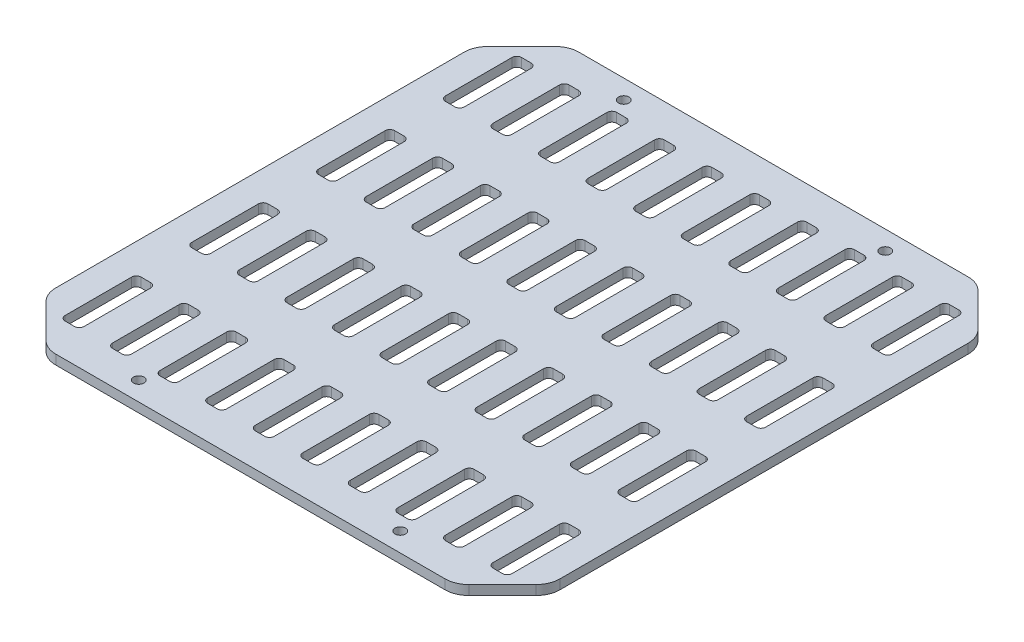
SolidWorks part; units mm, degrees
material "椴木"
ref_plane "前视基准面" through (0, 0, 0) normal (0, 0, 1) x (1, 0, 0)
ref_plane "上视基准面" through (0, 0, 0) normal (0, 1, 0) x (1, 0, 0)
ref_plane "右视基准面" through (0, 0, 0) normal (1, 0, 0) x (0, 0, -1)
sketch "草图1" plane through (0, 0, 0) normal (0, 1, 0) x (1, 0, 0)
  line L0 (-99.3153, 0) -> (94.5405, 0) construction
  line L1 (-53, 55) -> (53, 55)
  line L2 (-53, 55) -> (-53, -55)
  line L3 (-53, -55) -> (53, -55)
  line L4 (53, 55) -> (53, -55)
  line L5 (-53, 55) -> (53, -55) construction
  line L6 (-53, -55) -> (53, 55) construction
  line L7 (0, 84.1554) -> (0, -93.2275) construction
  line L8 (-61.5369, 40) -> (67.7359, 40) construction
  line L9 (-37, 48) -> (-37, 32)
  line L10 (-47, 48) -> (-43, 48)
  line L11 (-47, 48) -> (-47, 32)
  line L12 (-47, 32) -> (-43, 32)
  line L13 (-43, 48) -> (-43, 32)
  line L14 (-47, 48) -> (-43, 32) construction
  line L15 (-47, 32) -> (-43, 48) construction
  line L16 (-37, 48) -> (-33, 48)
  line L17 (-33, 48) -> (-33, 32)
  line L18 (-37, 32) -> (-33, 32)
  line L19 (-27, 48) -> (-27, 32)
  line L20 (-27, 48) -> (-23, 48)
  line L21 (-23, 48) -> (-23, 32)
  line L22 (-27, 32) -> (-23, 32)
  line L23 (-17, 48) -> (-17, 32)
  line L24 (-17, 48) -> (-13, 48)
  line L25 (-13, 48) -> (-13, 32)
  line L26 (-17, 32) -> (-13, 32)
  line L27 (-7, 48) -> (-7, 32)
  line L28 (-7, 48) -> (-3, 48)
  line L29 (-3, 48) -> (-3, 32)
  line L30 (-7, 32) -> (-3, 32)
  line L31 (3, 48) -> (3, 32)
  line L32 (3, 48) -> (7, 48)
  line L33 (7, 48) -> (7, 32)
  line L34 (3, 32) -> (7, 32)
  line L35 (13, 48) -> (13, 32)
  line L36 (13, 48) -> (17, 48)
  line L37 (17, 48) -> (17, 32)
  line L38 (13, 32) -> (17, 32)
  line L39 (23, 48) -> (23, 32)
  line L40 (23, 48) -> (27, 48)
  line L41 (27, 48) -> (27, 32)
  line L42 (23, 32) -> (27, 32)
  line L43 (33, 48) -> (33, 32)
  line L44 (33, 48) -> (37, 48)
  line L45 (37, 48) -> (37, 32)
  line L46 (33, 32) -> (37, 32)
  line L47 (43, 48) -> (43, 32)
  line L48 (43, 48) -> (47, 48)
  line L49 (47, 48) -> (47, 32)
  line L50 (43, 32) -> (47, 32)
  line L51 (-37, 21.3333) -> (-37, 5.3333)
  line L52 (-37, 21.3333) -> (-33, 21.3333)
  line L53 (-33, 21.3333) -> (-33, 5.3333)
  line L54 (-37, 5.3333) -> (-33, 5.3333)
  line L55 (-27, 21.3333) -> (-27, 5.3333)
  line L56 (-27, 21.3333) -> (-23, 21.3333)
  line L57 (-23, 21.3333) -> (-23, 5.3333)
  line L58 (-27, 5.3333) -> (-23, 5.3333)
  line L59 (-17, 21.3333) -> (-17, 5.3333)
  line L60 (-17, 21.3333) -> (-13, 21.3333)
  line L61 (-13, 21.3333) -> (-13, 5.3333)
  line L62 (-17, 5.3333) -> (-13, 5.3333)
  line L63 (-7, 21.3333) -> (-7, 5.3333)
  line L64 (-7, 21.3333) -> (-3, 21.3333)
  line L65 (-3, 21.3333) -> (-3, 5.3333)
  line L66 (-7, 5.3333) -> (-3, 5.3333)
  line L67 (3, 21.3333) -> (3, 5.3333)
  line L68 (3, 21.3333) -> (7, 21.3333)
  line L69 (7, 21.3333) -> (7, 5.3333)
  line L70 (3, 5.3333) -> (7, 5.3333)
  line L71 (13, 21.3333) -> (13, 5.3333)
  line L72 (13, 21.3333) -> (17, 21.3333)
  line L73 (17, 21.3333) -> (17, 5.3333)
  line L74 (13, 5.3333) -> (17, 5.3333)
  line L75 (23, 21.3333) -> (23, 5.3333)
  line L76 (23, 21.3333) -> (27, 21.3333)
  line L77 (27, 21.3333) -> (27, 5.3333)
  line L78 (23, 5.3333) -> (27, 5.3333)
  line L79 (33, 21.3333) -> (33, 5.3333)
  line L80 (33, 21.3333) -> (37, 21.3333)
  line L81 (37, 21.3333) -> (37, 5.3333)
  line L82 (33, 5.3333) -> (37, 5.3333)
  line L83 (43, 21.3333) -> (43, 5.3333)
  line L84 (43, 21.3333) -> (47, 21.3333)
  line L85 (47, 21.3333) -> (47, 5.3333)
  line L86 (43, 5.3333) -> (47, 5.3333)
  line L87 (-37, -5.3333) -> (-37, -21.3333)
  line L88 (-37, -5.3333) -> (-33, -5.3333)
  line L89 (-33, -5.3333) -> (-33, -21.3333)
  line L90 (-37, -21.3333) -> (-33, -21.3333)
  line L91 (-27, -5.3333) -> (-27, -21.3333)
  line L92 (-27, -5.3333) -> (-23, -5.3333)
  line L93 (-23, -5.3333) -> (-23, -21.3333)
  line L94 (-27, -21.3333) -> (-23, -21.3333)
  line L95 (-17, -5.3333) -> (-17, -21.3333)
  line L96 (-17, -5.3333) -> (-13, -5.3333)
  line L97 (-13, -5.3333) -> (-13, -21.3333)
  line L98 (-17, -21.3333) -> (-13, -21.3333)
  line L99 (-7, -5.3333) -> (-7, -21.3333)
  line L100 (-7, -5.3333) -> (-3, -5.3333)
  line L101 (-3, -5.3333) -> (-3, -21.3333)
  line L102 (-7, -21.3333) -> (-3, -21.3333)
  line L103 (3, -5.3333) -> (3, -21.3333)
  line L104 (3, -5.3333) -> (7, -5.3333)
  line L105 (7, -5.3333) -> (7, -21.3333)
  line L106 (3, -21.3333) -> (7, -21.3333)
  line L107 (13, -5.3333) -> (13, -21.3333)
  line L108 (13, -5.3333) -> (17, -5.3333)
  line L109 (17, -5.3333) -> (17, -21.3333)
  line L110 (13, -21.3333) -> (17, -21.3333)
  line L111 (23, -5.3333) -> (23, -21.3333)
  line L112 (23, -5.3333) -> (27, -5.3333)
  line L113 (27, -5.3333) -> (27, -21.3333)
  line L114 (23, -21.3333) -> (27, -21.3333)
  line L115 (33, -5.3333) -> (33, -21.3333)
  line L116 (33, -5.3333) -> (37, -5.3333)
  line L117 (37, -5.3333) -> (37, -21.3333)
  line L118 (33, -21.3333) -> (37, -21.3333)
  line L119 (43, -5.3333) -> (43, -21.3333)
  line L120 (43, -5.3333) -> (47, -5.3333)
  line L121 (47, -5.3333) -> (47, -21.3333)
  line L122 (43, -21.3333) -> (47, -21.3333)
  line L123 (-37, -32) -> (-37, -48)
  line L124 (-37, -32) -> (-33, -32)
  line L125 (-33, -32) -> (-33, -48)
  line L126 (-37, -48) -> (-33, -48)
  line L127 (-27, -32) -> (-27, -48)
  line L128 (-27, -32) -> (-23, -32)
  line L129 (-23, -32) -> (-23, -48)
  line L130 (-27, -48) -> (-23, -48)
  line L131 (-17, -32) -> (-17, -48)
  line L132 (-17, -32) -> (-13, -32)
  line L133 (-13, -32) -> (-13, -48)
  line L134 (-17, -48) -> (-13, -48)
  line L135 (-7, -32) -> (-7, -48)
  line L136 (-7, -32) -> (-3, -32)
  line L137 (-3, -32) -> (-3, -48)
  line L138 (-7, -48) -> (-3, -48)
  line L139 (3, -32) -> (3, -48)
  line L140 (3, -32) -> (7, -32)
  line L141 (7, -32) -> (7, -48)
  line L142 (3, -48) -> (7, -48)
  line L143 (13, -32) -> (13, -48)
  line L144 (13, -32) -> (17, -32)
  line L145 (17, -32) -> (17, -48)
  line L146 (13, -48) -> (17, -48)
  line L147 (23, -32) -> (23, -48)
  line L148 (23, -32) -> (27, -32)
  line L149 (27, -32) -> (27, -48)
  line L150 (23, -48) -> (27, -48)
  line L151 (33, -32) -> (33, -48)
  line L152 (33, -32) -> (37, -32)
  line L153 (37, -32) -> (37, -48)
  line L154 (33, -48) -> (37, -48)
  line L155 (43, -32) -> (43, -48)
  line L156 (43, -32) -> (47, -32)
  line L157 (47, -32) -> (47, -48)
  line L158 (43, -48) -> (47, -48)
  line L159 (-47, 21.3333) -> (-47, 5.3333)
  line L160 (-47, 21.3333) -> (-43, 21.3333)
  line L161 (-43, 21.3333) -> (-43, 5.3333)
  line L162 (-47, 5.3333) -> (-43, 5.3333)
  line L163 (-47, -5.3333) -> (-47, -21.3333)
  line L164 (-47, -5.3333) -> (-43, -5.3333)
  line L165 (-43, -5.3333) -> (-43, -21.3333)
  line L166 (-47, -21.3333) -> (-43, -21.3333)
  line L167 (-47, -32) -> (-47, -48)
  line L168 (-47, -32) -> (-43, -32)
  line L169 (-43, -32) -> (-43, -48)
  line L170 (-47, -48) -> (-43, -48)
  circle A0 centre (-27.5, 51) radius 1.1
  circle A1 centre (-27.5, 29) radius 1.1 construction
  circle A2 centre (27.5, 29) radius 1.1 construction
  circle A3 centre (27.5, 51) radius 1.1
  circle A4 centre (27.5, -29) radius 1.1 construction
  circle A5 centre (27.5, -51) radius 1.1
  circle A6 centre (-27.5, -29) radius 1.1 construction
  circle A7 centre (-27.5, -51) radius 1.1
  point P0 (0, 0)
  point P28 (-50.0057, 20.3333)
  point P29 (-45, 40)
  dimension "D3" = 2.2
  dimension "D1" = 106
  dimension "D2" = 110
  dimension "D4" = 22
  dimension "D5" = 55
  dimension "D6" = 102
  dimension "D7" = 4
  dimension "D8" = 16
  dimension "D9" = 6
  dimension "D10" = 10
  dimension "D11" = 4
extrude "凸台-拉伸1" add sketch "草图1" along normal blind 2
chamfer "倒角1" distance 10 angle 45 4 edges at (53, 1, -55) (53, 1, 55) (-53, 1, 55) (-53, 1, -55)
fillet "圆角1" radius 5 8 edges at (-53, 1, 45) (-43, 1, 55) (43, 1, 55) (53, 1, 45) (53, 1, -45) (43, 1, -55) (-43, 1, -55) (-53, 1, -45)
fillet "圆角2" radius 1 160 edges at (-43, 1, 32) (-47, 1, 32) (-47, 1, 48) (-43, 1, 48) (-43, 1, 5.3333) (-47, 1, 5.3333) (-47, 1, 21.3333) (-43, 1, 21.3333) (-43, 1, -21.3333) (-47, 1, -21.3333) (-47, 1, -5.3333) (-43, 1, -5.3333) (47, 1, 32) (43, 1, 32) (43, 1, 48) (47, 1, 48) (37, 1, 32) (33, 1, 32) (33, 1, 48) (37, 1, 48) (27, 1, 32) (23, 1, 32) (23, 1, 48) (27, 1, 48) (17, 1, 32) (13, 1, 32) (13, 1, 48) (17, 1, 48) (7, 1, 32) (3, 1, 32) (3, 1, 48) (7, 1, 48) (-3, 1, 32) (-7, 1, 32) (-7, 1, 48) (-3, 1, 48) (-13, 1, 32) (-17, 1, 32) (-17, 1, 48) (-13, 1, 48) (-23, 1, 32) (-27, 1, 32) (-27, 1, 48) (-23, 1, 48) (-33, 1, 32) (-37, 1, 32) (-37, 1, 48) (-33, 1, 48) (47, 1, 5.3333) (43, 1, 5.3333) (43, 1, 21.3333) (47, 1, 21.3333) (37, 1, 5.3333) (33, 1, 5.3333) (33, 1, 21.3333) (37, 1, 21.3333) (27, 1, 5.3333) (23, 1, 5.3333) (23, 1, 21.3333) (27, 1, 21.3333) (17, 1, 5.3333) (13, 1, 5.3333) (13, 1, 21.3333) (17, 1, 21.3333) (7, 1, 5.3333) (3, 1, 5.3333) (3, 1, 21.3333) (7, 1, 21.3333) (-3, 1, 5.3333) (-7, 1, 5.3333) (-7, 1, 21.3333) (-3, 1, 21.3333) (-13, 1, 5.3333) (-17, 1, 5.3333) (-17, 1, 21.3333) (-13, 1, 21.3333) (-23, 1, 5.3333) (-27, 1, 5.3333) (-27, 1, 21.3333) (-23, 1, 21.3333) (-33, 1, 5.3333) (-37, 1, 5.3333) (-37, 1, 21.3333) (-33, 1, 21.3333) (47, 1, -21.3333) (43, 1, -21.3333) (43, 1, -5.3333) (47, 1, -5.3333) (37, 1, -21.3333) (33, 1, -21.3333) (33, 1, -5.3333) (37, 1, -5.3333) (27, 1, -21.3333) (23, 1, -21.3333) (23, 1, -5.3333) (27, 1, -5.3333) (17, 1, -21.3333) (13, 1, -21.3333) (13, 1, -5.3333) (17, 1, -5.3333) (7, 1, -21.3333) (3, 1, -21.3333) (3, 1, -5.3333) (7, 1, -5.3333) (-3, 1, -21.3333) (-7, 1, -21.3333) (-7, 1, -5.3333) (-3, 1, -5.3333) (-13, 1, -21.3333) (-17, 1, -21.3333) (-17, 1, -5.3333) (-13, 1, -5.3333) (-23, 1, -21.3333) (-27, 1, -21.3333) (-27, 1, -5.3333) (-23, 1, -5.3333) (-33, 1, -21.3333) (-37, 1, -21.3333) (-37, 1, -5.3333) (-33, 1, -5.3333) (47, 1, -48) (43, 1, -48) (43, 1, -32) (47, 1, -32) (37, 1, -48) (33, 1, -48) (33, 1, -32) (37, 1, -32) (27, 1, -48) (23, 1, -48) (23, 1, -32) (27, 1, -32) (17, 1, -48) (13, 1, -48) (13, 1, -32) (17, 1, -32) (7, 1, -48) (3, 1, -48) (3, 1, -32) (7, 1, -32) (-3, 1, -48) (-7, 1, -48) (-7, 1, -32) (-3, 1, -32) (-13, 1, -48) (-17, 1, -48) (-17, 1, -32) (-13, 1, -32) (-23, 1, -48) (-27, 1, -48) (-27, 1, -32) (-23, 1, -32) (-33, 1, -48) (-37, 1, -48) (-37, 1, -32) (-33, 1, -32) (-47, 1, -32) (-43, 1, -32) (-43, 1, -48) (-47, 1, -48)
